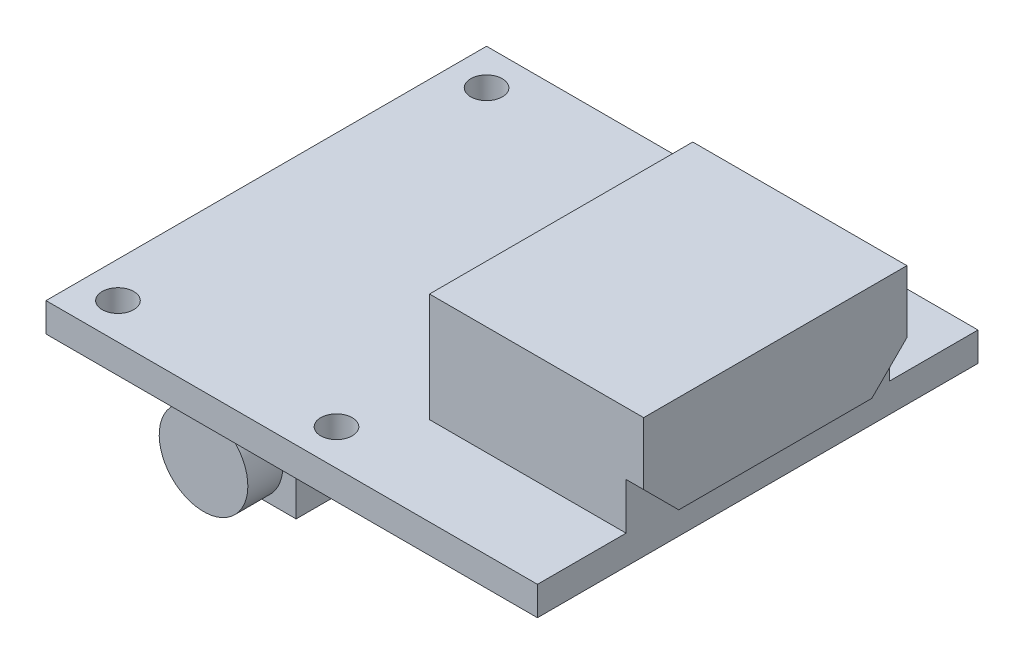
SolidWorks part; units mm, degrees
ref_plane "Front" through (0, 0, 0) normal (0, 0, 1) x (1, 0, 0)
ref_plane "Top" through (0, 0, 0) normal (0, 1, 0) x (1, 0, 0)
ref_plane "Right" through (0, 0, 0) normal (1, 0, 0) x (0, 0, -1)
sketch "Sketch1" plane through (0, 0, 0) normal (0, 1, 0) x (1, 0, 0)
  line L1 (-14, -12.55) -> (14, -12.55)
  line L2 (-14, -12.55) -> (-14, 12.55)
  line L3 (-14, 12.55) -> (14, 12.55)
  line L4 (14, -12.55) -> (14, 12.55)
  line L5 (-14, -12.55) -> (14, 12.55) construction
  line L6 (-14, 12.55) -> (14, -12.55) construction
  point P0 (0, 0)
  dimension "D1" = 28
  dimension "D2" = 25.1
extrude "Boss-Extrude1" add sketch "Sketch1" along normal blind 1.65
sketch "Sketch2" plane through (0, 1.65, 0) normal (0, 1, 0) x (1, 0, 0)
  line L0 (14, -12.55) -> (14, 12.55) construction
  line L1 (14, 7.5) -> (2.8, 7.5)
  line L2 (14, 7.5) -> (14, -7.5)
  line L3 (14, -7.5) -> (2.8, -7.5)
  line L4 (2.8, 7.5) -> (2.8, -7.5)
  point P6 (14, 0)
  dimension "D1" = 11.2
  dimension "D2" = 15
extrude "Boss-Extrude2" add sketch "Sketch2" along normal blind 6.2
sketch "Sketch3" plane through (14, 0, 0) normal (1, 0, 0) x (0, 0, -1)
  line L0 (-7.5, 4.3) -> (-7.5, 7.85)
  line L1 (-7.5, 7.85) -> (-7.5, 1.65) construction
  line L2 (-7.5, 7.85) -> (7.5, 7.85)
  line L3 (7.5, 7.85) -> (7.5, 4.3)
  line L4 (7.5, 7.85) -> (7.5, 1.65) construction
  line L5 (-7.5, 4.3) -> (-5.5, 2.3)
  line L6 (-5.5, 2.3) -> (5.5, 2.3)
  line L7 (5.5, 2.3) -> (7.5, 4.3)
  dimension "D1" = 5.55
  dimension "D2" = 11
  dimension "D3" = 45
extrude "Boss-Extrude3" add sketch "Sketch3" along normal blind 1
sketch "Sketch4" plane through (0, 0, 0) normal (0, -1, 0) x (1, 0, 0)
  line L0 (-14, -12.55) -> (-14, 12.55) construction
  line L1 (-8.8, 10.05) -> (-2.25, 10.05)
  line L2 (-8.8, 10.05) -> (-8.8, -1.9)
  line L3 (-8.8, -1.9) -> (-2.25, -1.9)
  line L4 (-2.25, 10.05) -> (-2.25, -1.9)
  line L5 (-14, 12.55) -> (14, 12.55) construction
  dimension "D1" = 5.2
  dimension "D2" = 6.55
  dimension "D3" = 11.95
  dimension "D4" = 2.5
extrude "Boss-Extrude4" add sketch "Sketch4" along normal blind 4.5
sketch "Sketch5" plane through (0, 0, 10.05) normal (0, 0, 1) x (1, 0, 0)
  line L0 (-8.8, -4.5) -> (-8.8, 0) construction
  line L1 (-2.25, -4.5) -> (-8.8, -4.5) construction
  circle A0 centre (-5.525, -2.25) radius 2.525
  point P5 (-8.8, -2.25)
  point P9 (-5.525, -4.5)
  dimension "D1" = 5.05
extrude "Boss-Extrude5" add sketch "Sketch5" along normal blind 2
sketch "Sketch6" plane through (0, 0, 0) normal (0, -1, 0) x (-1, 0, 0)
  line L0 (-0.5, -9.6) -> (-0.5, 9.6) construction
  line L1 (11.95, 10.5) -> (-0.5, 10.5) construction
  line L2 (11.95, 10.5) -> (11.95, -10.5) construction
  line L3 (11.95, -10.5) -> (-0.5, -10.5) construction
  line L4 (-0.5, 10.5) -> (-0.5, -10.5) construction
  line L5 (11.95, 10.5) -> (-0.5, -10.5) construction
  line L6 (11.95, -10.5) -> (-0.5, 10.5) construction
  line L7 (11.05, -10.5) -> (0.4, -10.5) construction
  line L8 (11.95, -10.5) -> (14, -10.5) construction
  line L9 (14, 12.55) -> (14, -12.55) construction
  line L10 (11.95, -10.5) -> (11.95, -12.55) construction
  line L11 (14, -12.55) -> (-14, -12.55) construction
  circle A0 centre (11.95, -10.5) radius 0.9
  circle A1 centre (11.95, 10.5) radius 0.9
  circle A2 centre (-0.5, 10.5) radius 0.9
  circle A3 centre (-0.5, -10.5) radius 0.9
  point P0 (5.725, 0)
  point P12 (10.3513, -10.5)
  dimension "D1" = 1.8
  dimension "D2" = 10.65
  dimension "D3" = 19.2
extrude "Cut-Extrude1" cut sketch "Sketch6" against normal through all
